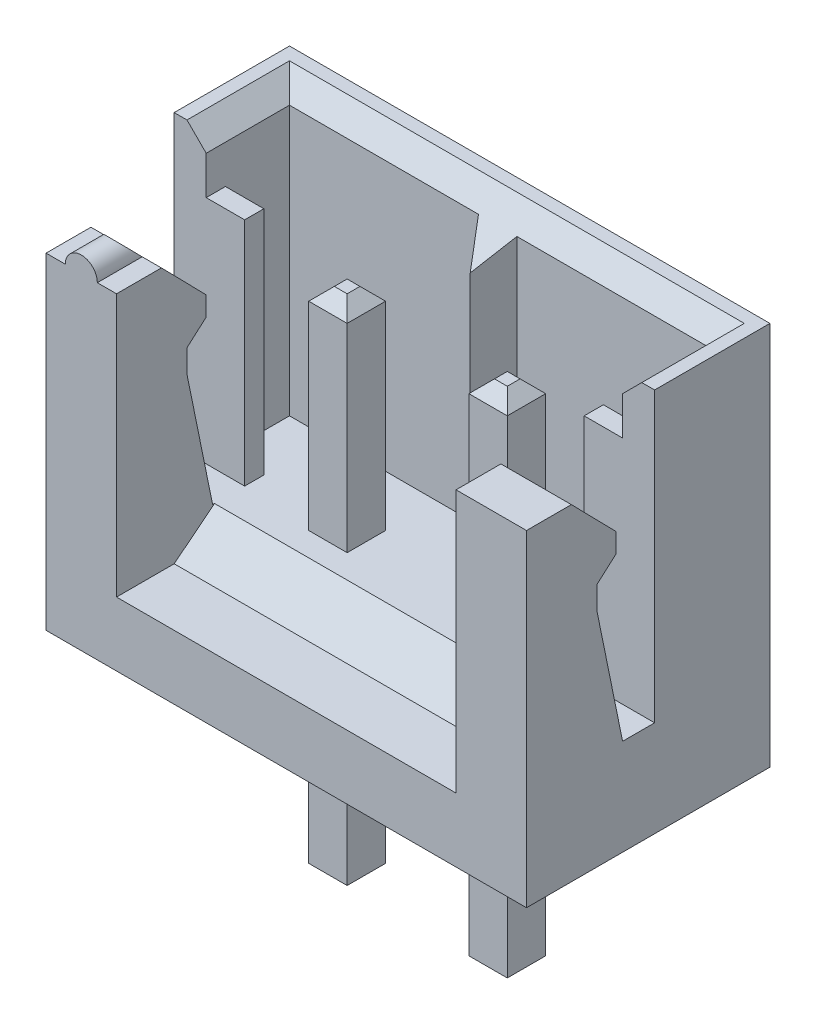
SolidWorks part; units mm, degrees
ref_plane "Спереди" through (0, 0, 0) normal (0, 0, 1) x (1, 0, 0)
ref_plane "Сверху" through (0, 0, 0) normal (0, 1, 0) x (1, 0, 0)
ref_plane "Справа" through (0, 0, 0) normal (1, 0, 0) x (0, 0, -1)
sketch "Эскиз1" plane through (0, 0, 0) normal (0, 1, 0) x (1, 0, 0)
  line L1 (0, 0) -> (7.5, 0)
  line L2 (0, 0) -> (0, -3.8)
  line L3 (0, -3.8) -> (7.5, -3.8)
  line L4 (7.5, 0) -> (7.5, -3.8)
  dimension "D1" = 7.5
  dimension "D2" = 3.8
extrude "Бобышка-Вытянуть1" add sketch "Эскиз1" along normal blind 6
sketch "Эскиз2" plane through (0, 6, 0) normal (0, 1, 0) x (1, 0, 0)
  line L0 (0, 0) -> (0, -3.8) construction
  line L1 (0.5, -0.5) -> (7, -0.5)
  line L2 (0.5, -0.5) -> (0.5, -1.5)
  line L3 (1.1, -3.3) -> (6.4, -3.3)
  line L5 (3.75, 0) -> (3.75, -3.8) construction
  line L6 (7.5, 0) -> (0, 0) construction
  line L7 (0, -3.8) -> (7.5, -3.8) construction
  line L9 (0.5, -1.5) -> (1.1, -1.5)
  line L10 (1.1, -1.5) -> (1.1, -3.3)
  line L11 (6.4, -1.5) -> (6.4, -3.3)
  line L12 (7, -1.5) -> (6.4, -1.5)
  line L13 (7, -0.5) -> (7, -1.5)
  line L14 (0.5, -1.5) -> (0.5, -1.8) construction
  line L15 (0.5, -1.8) -> (1.1, -1.8) construction
  point P13 (3.75, -3.3)
  point P14 (3.75, -0.5)
  point P16 (3.75, -3.3)
  point P20 (3.75, -0.5)
  dimension "D1" = 0.5
  dimension "D2" = 0.5
  dimension "D3" = 2.8
  dimension "D4" = 0.3
  dimension "D5" = 0.6
  dimension "D6" = 1.3
extrude "Вырез-Вытянуть1" cut sketch "Эскиз2" against normal blind 5
sketch "Эскиз3" plane through (0, 0, 0) normal (-1, 0, 0) x (0, 0, 1)
  line L0 (1.8, 6) -> (1.8, 1.5)
  line L1 (0, 6) -> (3.8, 6) construction
  line L2 (1.8, 1.5) -> (2.3, 1.5)
  line L3 (2.3, 1.5) -> (2.7, 3.4596)
  line L4 (0, 6) -> (0, 0) construction
  line L5 (3.8, 5.1) -> (3.1, 5.1)
  line L6 (3.8, 6) -> (3.8, 0) construction
  line L8 (3.1, 5.1) -> (2.4, 4.3859)
  line L9 (2.4, 4.3859) -> (2.4, 4.0859)
  line L10 (2.4, 4.0859) -> (2.7, 3.8213)
  line L11 (2.7, 3.8213) -> (2.7, 3.4596)
  line L12 (1.8, 6) -> (3.8, 6)
  line L13 (3.8, 6) -> (3.8, 5.1)
  dimension "D1" = 1.8
  dimension "D2" = 4.5
  dimension "D3" = 0.9
  dimension "D4" = 0.7
  dimension "D5" = 1.4
  dimension "D6" = 1.1
  dimension "D7" = 2
  dimension "D8" = 0.4
  dimension "D9" = 1
  dimension "D10" = 0.3
  dimension "D11" = 0.5
extrude "Вырез-Вытянуть2" cut sketch "Эскиз3" against normal through all
sketch "Эскиз4" plane through (0, 0, 3.8) normal (0, 0, 1) x (1, 0, 0)
  line L0 (0, 5.1) -> (1.1, 5.1) construction
  line L1 (7.5, 5.1) -> (0, 5.1) construction
  line L3 (0.3, 5.1) -> (0.8, 5.1)
  arc A0 (0.8, 5.1) -> (0.3, 5.1) centre (0.55, 5.1) ccw
  point P8 (0, 0)
  dimension "D1" = 0.5
  dimension "D2" = 1.1
extrude "Бобышка-Вытянуть2" add sketch "Эскиз4" against normal up to surface (0.7 mm away) up to face at (0.55, 4.7429, 2.75)
sketch "Эскиз5" plane through (0, 0, 3.8) normal (0, 0, 1) x (1, 0, 0)
  line L0 (7.5, 5.1) -> (0.8, 5.1) construction
  line L1 (1.1, 5.1) -> (6.4, 5.1)
  line L2 (1.1, 5.1) -> (1.1, 1)
  line L3 (1.1, 1) -> (6.4, 1)
  line L6 (0, 5.1) -> (0, 0) construction
  line L8 (3.75, 1) -> (3.75, 5.1) construction
  line L9 (6.4, 5.1) -> (6.4, 1)
  line L11 (0, 0) -> (7.5, 0) construction
  line L12 (3.75, 0) -> (3.75, 5.1) construction
  line L13 (1.1, 1) -> (6.4, 1) construction
  point P14 (3.75, 3.05)
  dimension "D1" = 1.1
extrude "Вырез-Вытянуть3" cut sketch "Эскиз5" against normal up to next
sketch "Эскиз6" plane through (0.5, 0, 0) normal (1, 0, 0) x (0, 0, -1)
  line L0 (-0.5, 1) -> (-1.5, 1) construction
  line L2 (-2.9, 1) -> (-2.27, 1.5)
  line L3 (-2.27, 1.5) -> (-0.5, 1.5)
  line L4 (-0.5, 1) -> (-0.5, 6) construction
  line L5 (-0.5, 1.5) -> (-0.5, 1)
  line L6 (-0.5, 1) -> (-2.9, 1)
  line L8 (-3.8, 5.1) -> (-3.8, 1) construction
  point P0 (-2.8028, 1)
  dimension "D1" = 0.5
  dimension "D2" = 1.77
  dimension "D3" = 0.9
extrude "Бобышка-Вытянуть3" add sketch "Эскиз6" along normal up to next
sketch "Эскиз9" plane through (0, 6, 0) normal (0, 1, 0) x (1, 0, 0)
  line L0 (3.45, -0.5) -> (3.75, -0.9284)
  line L1 (7, -0.5) -> (0.5, -0.5) construction
  line L2 (3.75, -0.5) -> (3.75, -0.9284) construction
  line L3 (7, -0.5) -> (0.5, -0.5) construction
  line L4 (4.05, -0.5) -> (3.75, -0.9284)
  line L5 (3.45, -0.5) -> (4.05, -0.5)
  dimension "D1" = 0.6
  dimension "D2" = 35
  dimension "D3" = 2.95
extrude "Бобышка-Вытянуть5" add sketch "Эскиз9" against normal up to next
sketch "Эскиз11" plane through (0, 0, 0) normal (0, -1, 0) x (1, 0, 0)
  line L1 (1.5, 3.2) -> (3.5, 3.2)
  line L2 (1.5, 3.2) -> (1.5, 0)
  line L3 (1.5, 0) -> (3.5, 0)
  line L4 (3.5, 3.2) -> (3.5, 0)
  line L5 (1.5, 3.2) -> (3.5, 0) construction
  line L6 (1.5, 0) -> (3.5, 3.2) construction
  line L7 (7.5, 0) -> (0, 0) construction
  line L9 (2.1, 2) -> (2.9, 2)
  line L10 (2.1, 2) -> (2.1, 1.2)
  line L11 (2.1, 1.2) -> (2.9, 1.2)
  line L12 (2.9, 2) -> (2.9, 1.2)
  line L13 (2.1, 2) -> (2.9, 1.2) construction
  line L14 (2.1, 1.2) -> (2.9, 2) construction
  point P0 (2.5, 1.6)
  point P8 (2.5, 1.6)
  dimension "D1" = 2.5
  dimension "D2" = 1.6
  dimension "D3" = 2
  dimension "D4" = 0.8
extrude "Вырез-Вытянуть5" cut sketch "Эскиз11" against normal blind 0.3
sketch "Эскиз15" plane through (0, 0, 0) normal (0, -1, 0) x (1, 0, 0)
  line L0 (2.1, 2) -> (2.9, 1.2) construction
  circle A0 centre (2.5, 1.6) radius 0.05
  point P4 (2.5, 1.6)
  dimension "D1" = 0.1
extrude "Вырез-Вытянуть6" cut sketch "Эскиз15" against normal blind 0.1
ref_point "Точка1"
chamfer "Фаска7" distance 0.3 angle 45 7 edges at (1.5, 0.3, 1.6) (2.5, 0.3, 3.2) (3.5, 0.3, 1.6) (2.9, 0.3, 1.6) (2.5, 0.3, 2) (2.1, 0.3, 1.6) (2.5, 0.3, 1.2)
pattern_linear "Линейный массив2" [suppressed] count 1 spacing 2.5 of bodies 115
sketch "Эскиз7" plane through (0, 0, 0) normal (0, -1, 0) x (1, 0, 0)
  line L0 (7.5, 0) -> (3.5, 0) construction
  line L1 (2.2, 1.9) -> (2.8, 1.9)
  line L2 (2.2, 1.9) -> (2.2, 1.3)
  line L3 (2.2, 1.3) -> (2.8, 1.3)
  line L4 (2.8, 1.9) -> (2.8, 1.3)
  line L5 (2.2, 1.9) -> (2.8, 1.3) construction
  line L6 (2.2, 1.3) -> (2.8, 1.9) construction
  line L7 (0, 0) -> (0, 3.8) construction
  point P0 (2.5, 1.6)
  dimension "D1" = 0.6
  dimension "D2" = 1.6
  dimension "D3" = 2.5
extrude "Бобышка-Вытянуть4" add sketch "Эскиз7" against normal blind 4.8 and the other way blind 3.2
chamfer "Фаска6" distance 0.2 angle 45 8 edges at (2.5, -3.2, 1.3) (2.2, -3.2, 1.6) (2.5, -3.2, 1.9) (2.8, -3.2, 1.6) (2.5, 4.8, 1.9) (2.2, 4.8, 1.6) (2.5, 4.8, 1.3) (2.8, 4.8, 1.6)
pattern_linear "Линейный массив1" count 2 spacing 2.5 along (1, 0, 0) of "Бобышка-Вытянуть4", "Фаска6", "Фаска7", "Вырез-Вытянуть5"
sketch "Эскиз10" plane through (0.5, 0, 0) normal (1, 0, 0) x (0, 0, -1)
  line L0 (-1, 6) -> (-0.2, 6)
  line L1 (-0.2, 6) -> (-1, 5.2)
  line L3 (-1, 5.2) -> (-1, 5.1)
  line L4 (-0.5, 6) -> (-1.5, 6) construction
  line L5 (-1, 5.1) -> (-1.8, 5.1)
  line L6 (-1.8, 5.1) -> (-1.8, 6)
  line L7 (-1.8, 6) -> (-1, 6)
  line L8 (-1, 6) -> (-1, 5.1) construction
  dimension "D1" = 45
  dimension "D2" = 0.9
  dimension "D3" = 0.8
  dimension "D4" = 0.8
extrude "Вырез-Вытянуть4" cut sketch "Эскиз10" along normal up to surface (6.5 mm away) contours L1 L3 L5 L6 L7 L0 up to face at (7, 3.75, 1)
chamfer "Фаска5" distance 0.3 angle 45 2 edges at (7, 6, 1) (0.5, 6, 1)
equation "\"PINS\" = 2"
equation "\"D1@Линейный массив2\"= \"GUIDE_MASS\""
equation "\"PIN_MASS\"= \"PINS\""
equation "\"D1@Линейный массив1\"=\"PIN_MASS\""
equation "\"GUIDE_MASS\" = \"PINS\" - 1"
equation "\"D1@Эскиз1\"= 5 + ( 2.5 * ( \"PIN_MASS\" - 1 ) )"
